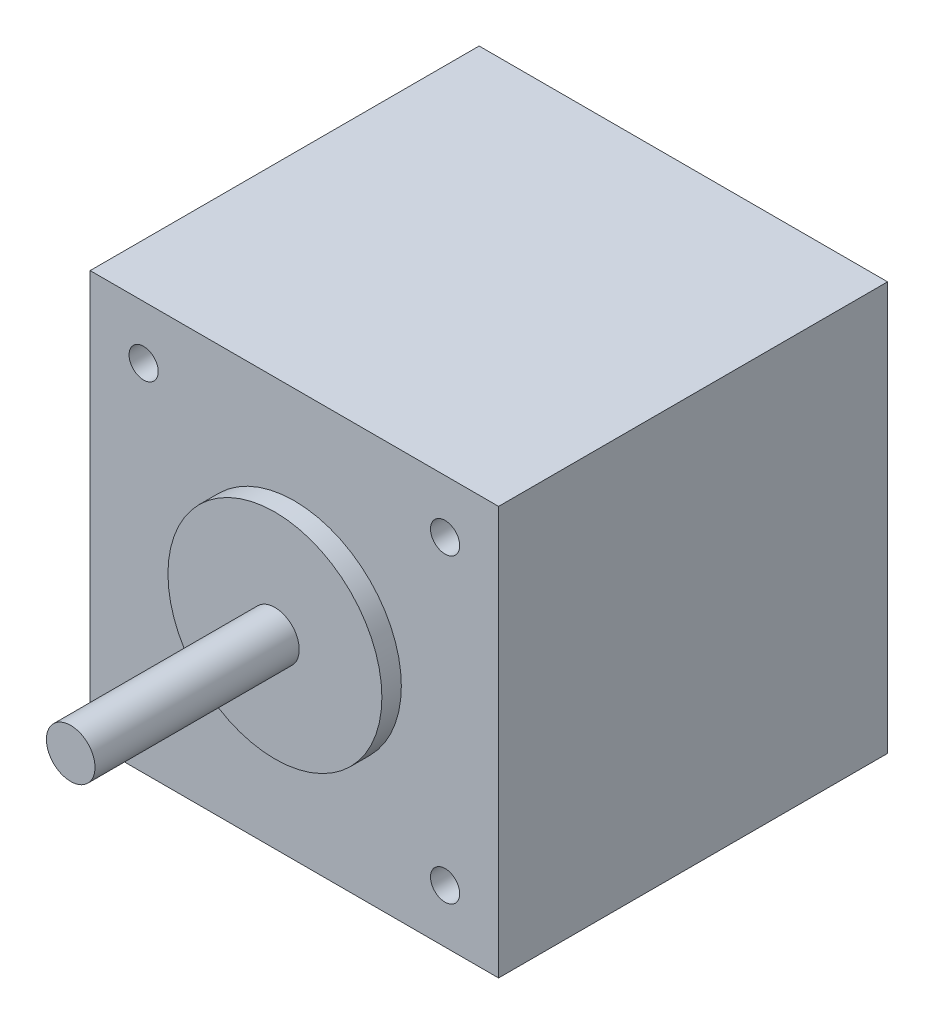
SolidWorks part; units mm, degrees
ref_plane "Спереди" through (0, 0, 0) normal (0, 0, 1) x (1, 0, 0)
ref_plane "Сверху" through (0, 0, 0) normal (0, 1, 0) x (1, 0, 0)
ref_plane "Справа" through (0, 0, 0) normal (1, 0, 0) x (0, 0, -1)
other "Configuration Table"
sketch "Эскиз1" plane through (0, 0, 0) normal (0, 0, 1) x (1, 0, 0)
  line L1 (-21, -21) -> (21, -21)
  line L2 (-21, -21) -> (-21, 21)
  line L3 (-21, 21) -> (21, 21)
  line L4 (21, -21) -> (21, 21)
  line L5 (-21, -21) -> (21, 21) construction
  line L6 (-21, 21) -> (21, -21) construction
  point P0 (0, 0)
  dimension "D1" = 42
  dimension "D2" = 42
extrude "Корпус" add sketch "Эскиз1" along normal blind 40
sketch "Эскиз2" plane through (0, 0, 0) normal (0, 0, 1) x (1, 0, 0)
  circle A0 centre (0, 0) radius 2.5
extrude "Вал_ПРЕДВ" add sketch "Эскиз2" along normal blind 63
sketch "Эскиз3" plane through (0, 0, 0) normal (0, 0, 1) x (1, 0, 0)
  circle A0 centre (0, 0) radius 11
  dimension "D1" = 22
extrude "Буртик_ПРЕДВ" add sketch "Эскиз3" along normal blind 42
sketch "Эскиз4" plane through (0, 0, 0) normal (0, 0, 1) x (1, 0, 0)
  circle A0 centre (-15.5, -15.5) radius 1.5
  circle A1 centre (-15.5, 15.5) radius 1.5
  circle A2 centre (15.5, -15.5) radius 1.5
  circle A3 centre (15.5, 15.5) radius 1.5
  dimension "D1" = 3
  dimension "D2" = 3
  dimension "D3" = 3
  dimension "D4" = 3
extrude "Крепеж_М3_ПРЕДВ" cut sketch "Эскиз4" against normal blind 4.5 from offset 40
equation "\"Мотор X ширина корпуса\"= 42.3"
equation "\"Мотор X высота корпуса\"= 42.3"
equation "\"Мотор X длина корпуса\"= 40"
equation "\"Мотор X вылет вала\"= 19.8"
equation "\"Мотор Y ширина корпуса\"= 42.3"
equation "\"Мотор Y высота корпуса\"= 42.3"
equation "\"Мотор Y длина корпуса\"= 48"
equation "\"Мотор Y вылет вала\"= 30"
equation "\"Мотор Z ширина корпуса\"= 42"
equation "\"Мотор Z высота корпуса\"= 42"
equation "\"Мотор Z длина корпуса\"= 40"
equation "\"Мотор Z вылет вала\"= 23"
equation "\"Мотор диаметр вала ПРЕДВ\"= 5"
equation "\"Мотор шаг крепления ПРЕДВ\"= 31"
equation "\"Мотор диаметр отверстий ПРЕДВ\"= 3"
equation "\"Мотор глубина отверстий ПРЕДВ\"= 4.5"
equation "\"Мотор диаметр буртика ПРЕДВ\"= 22"
equation "\"Мотор высота буртика ПРЕДВ\"= 2"
equation "\"Мотор диаметр шкива ПРЕДВ\"= 16"
equation "\"Мотор длина шкива ПРЕДВ\"= 12"
equation "\"Мотор отступ шкива ПРЕДВ\"= 5"
equation "\"Мотор X шаг градусов\"= 1.8"
equation "\"Мотор X ток А\"= 1.5"
equation "\"Мотор X сопротивление Ом\"= 1.3"
equation "\"Мотор X индуктивность мГн\"= 2"
equation "\"Мотор Y шаг градусов\"= 1.8"
equation "\"Мотор Y ток А\"= 2.2"
equation "\"Мотор Y сопротивление Ом\"= 0.9"
equation "\"Мотор Y индуктивность мГн\"= 2"
equation "\"Мотор Z шаг градусов\"= 1.8"
equation "\"Мотор Z ток А\"= 1"
equation "\"Мотор Z сопротивление Ом\"= 4"
equation "\"Мотор Z индуктивность мГн\"= 8"
equation "\"Мотор Y диаметр ротора\"= 25.78"
equation "\"D1@Эскиз1\" = \"Мотор Z ширина корпуса\""
equation "\"D2@Эскиз1\" = \"Мотор Z высота корпуса\""
equation "\"D1@Корпус\" = \"Мотор Z длина корпуса\""
equation "\"D1@Эскиз2\" = \"Мотор диаметр вала ПРЕДВ\""
equation "\"D1@Вал_ПРЕДВ\" = \"Мотор Z длина корпуса\" + \"Мотор Z вылет вала\""
equation "\"D1@Эскиз3\" = \"Мотор диаметр буртика ПРЕДВ\""
equation "\"D1@Буртик_ПРЕДВ\" = \"Мотор Z длина корпуса\" + \"Мотор высота буртика ПРЕДВ\""
equation "\"D1@Эскиз4\" = \"Мотор диаметр отверстий ПРЕДВ\""
equation "\"D2@Эскиз4\" = \"Мотор диаметр отверстий ПРЕДВ\""
equation "\"D3@Эскиз4\" = \"Мотор диаметр отверстий ПРЕДВ\""
equation "\"D4@Эскиз4\" = \"Мотор диаметр отверстий ПРЕДВ\""
equation "\"D1@Крепеж_М3_ПРЕДВ\" = \"Мотор глубина отверстий ПРЕДВ\""
equation "\"D19@Крепеж_М3_ПРЕДВ\" = \"Мотор Z длина корпуса\""
equation "\"Ширина груза\"= 420"
equation "\"Глубина груза\"= 490"
equation "\"Высота груза\"= 297"
equation "\"Ширина ячейки\"= \"Ширина груза\" + 10"
equation "\"Глубина ячейки\"= \"Глубина груза\" + 10"
equation "\"Высота ячейки\"= \"Высота груза\" + 10 + 13"
equation "\"Колво ячеек ширина\"= 2"
equation "\"Колво ячеек высота\"= 2"
equation "\"Толщина стенки\"= 10"
equation "\"Крепление дверцы\"= 5"
equation "\"Ширина рейки\"= \"Толщина шестерни\""
equation "\"Высота рейки\"= 20"
equation "\"Высота пола\"= 20"
equation "\"Колво полозьев\"= 5"
equation "\"Отступ рейки\"= 20"
equation "\"Глубина каретки\"= \"Глубина ячейки\" + 30 + \"Мотор Y высота корпуса\" + 20"
equation "\"Отступ шпильки\"= 20"
equation "\"Диаметр шпильки\"= 5"
equation "\"Длинна шпильки\"= ( \"Высота ячейки\" + \"Толщина стенки\" + \"Высота пола\" ) * \"Колво ячеек высота\" + ( \"Толщина стенки\" + \"Отступ рейки\" ) * 2 "
equation "\"Ширина пластины\"= 50  "
equation "\"Высота зона выгрузки\"= \"Высота ячейки\" * 2 + \"Толщина стенки\" * 2"
equation "\"Колво выгрузки\"= 1"
equation "\"Отступ крепления мотора фиксации\" = 30"
equation "\"Диаметр оси\"= 10"
equation "\"Диаметр ролика\"= 20"
equation "\"Колво роликов\"= 10"
equation "\"Шаг роликов\"= \"Диаметр ролика\" + 20"
equation "\"Ширина ячейки выгрузки\"= \"Ширина ячейки\" + \"Толщина стенки\" + \"Отступ крепления мотора фиксации\"*2"
equation "\"Длинна рейки\"= ( \"Ширина ячейки\" + \"Толщина стенки\" + \"Крепление дверцы\" ) * \"Колво ячеек ширина\" + \"Ширина ячейки выгрузки\" * \"Колво выгрузки\" + \"Толщина стенки\""
